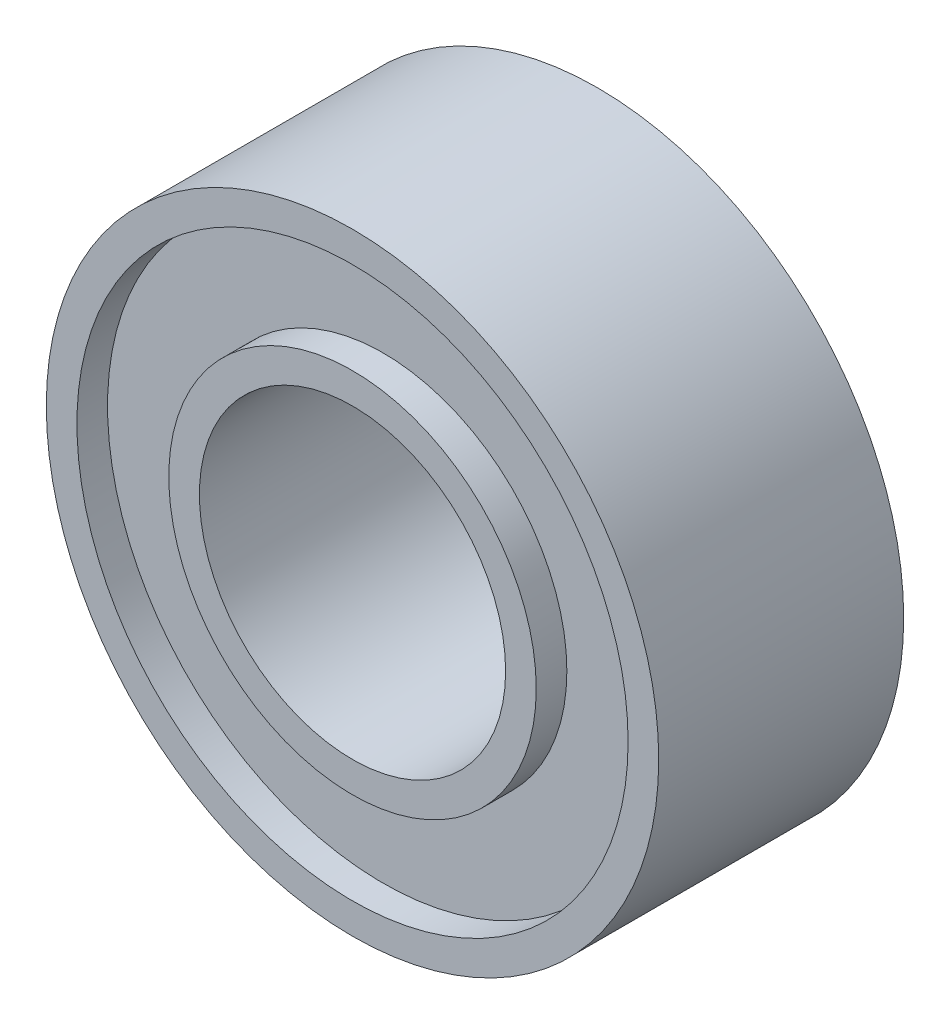
SolidWorks part; units mm, degrees
ref_plane "前视基准面" through (0, 0, 0) normal (0, 0, 1) x (1, 0, 0)
ref_plane "上视基准面" through (0, 0, 0) normal (0, 1, 0) x (1, 0, 0)
ref_plane "右视基准面" through (0, 0, 0) normal (1, 0, 0) x (0, 0, -1)
sketch "草图2" plane through (0, 0, 0) normal (0, 0, 1) x (1, 0, 0)
  circle A0 centre (0, 0) radius 5
  circle A1 centre (0, 0) radius 2.5
extrude "凸台-拉伸1" add sketch "草图2" along normal blind 4
sketch "草图3" plane through (0, 0, 4) normal (0, 0, 1) x (1, 0, 0)
  circle A0 centre (0, 0) radius 3
  circle A1 centre (0, 0) radius 4.5
extrude "切除-拉伸1" cut sketch "草图3" against normal blind 0.5
extrude "切除-拉伸2" cut sketch "草图3<2>" along normal blind 0.5 from surface starting at face at (5, 0, 0)
sketch "草图3<2>" plane through (0, 0, 4) normal (0, 0, 1) x (1, 0, 0) same geometry as "草图3"
